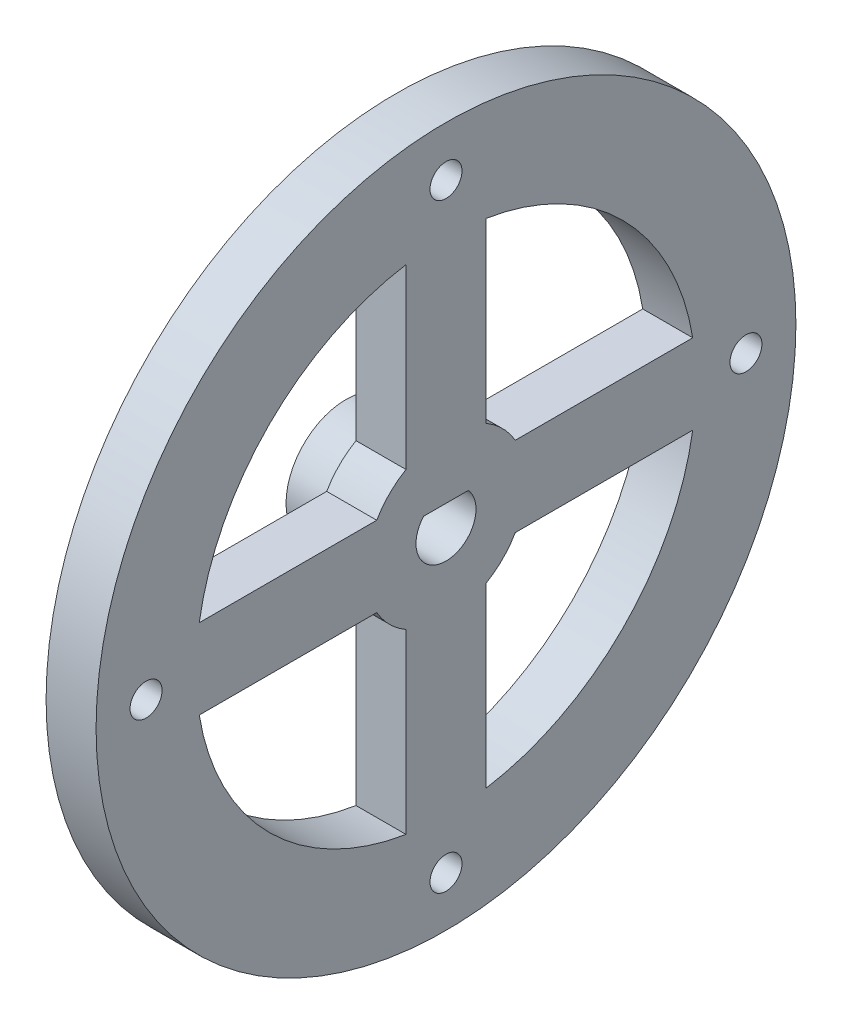
SolidWorks part; units mm, degrees
material "PLA (White)"
ref_plane "Front Plane" through (0, 0, 0) normal (0, 0, 1) x (1, 0, 0)
ref_plane "Top Plane" through (0, 0, 0) normal (0, 1, 0) x (1, 0, 0)
ref_plane "Right Plane" through (0, 0, 0) normal (1, 0, 0) x (0, 0, -1)
sketch "Sketch1" plane through (0, 0, 0) normal (1, 0, 0) x (0, 0, -1)
  line L0 (0, 0) -> (0, 50000) construction
  line L1 (4, 6.9282) -> (4, 24.6779)
  line L2 (-4, 24.6779) -> (-4, 6.9282)
  line L3 (-24.6779, -4) -> (-6.9282, -4)
  line L4 (-6.9282, 4) -> (-24.6779, 4)
  line L5 (4, -24.6779) -> (4, -6.9282)
  line L6 (-4, -6.9282) -> (-4, -24.6779)
  line L7 (24.6779, 4) -> (6.9282, 4)
  line L8 (6.9282, -4) -> (24.6779, -4)
  line L9 (-2.2361, 2) -> (2.2361, 2)
  circle A0 centre (0, 0) radius 35
  arc A1 (-2.2361, 2) -> (2.2361, 2) centre (0, 0) ccw
  arc A2 (-6.9282, -4) -> (-4, -6.9282) centre (0, 0) ccw
  arc A3 (-24.6779, -4) -> (-4, -24.6779) centre (0, 0) ccw
  arc A4 (-4, 6.9282) -> (-6.9282, 4) centre (0, 0) ccw
  arc A5 (24.6779, 4) -> (4, 24.6779) centre (0, 0) ccw
  arc A6 (4, -24.6779) -> (24.6779, -4) centre (0, 0) ccw
  arc A7 (4, -6.9282) -> (6.9282, -4) centre (0, 0) ccw
  arc A8 (6.9282, 4) -> (4, 6.9282) centre (0, 0) ccw
  arc A9 (-24.6779, 4) -> (-4, 24.6779) centre (0, 0) cw
  point P27 (0, 0)
  dimension "D1" = 70
  dimension "D2" = 6
  dimension "D5" = 16
  dimension "D6" = 50
  dimension "D3" = 8
  dimension "D7" = 2
  dimension "D4" = 4
extrude "Boss-Extrude1" add sketch "Sketch1" along normal blind 5
sketch "Sketch2" plane through (0, 0, 0) normal (-1, 0, 0) x (0, 0, 1)
  circle A0 centre (0, 0) radius 30 construction
  circle A1 centre (0, 30) radius 1.6
  circle A2 centre (30, 0) radius 1.6
  circle A3 centre (0, -30) radius 1.6
  circle A4 centre (-30, 0) radius 1.6
  point P14 (0, 0)
  dimension "D1" = 60
  dimension "D2" = 3.2
  dimension "D3" = 4
extrude "Cut-Extrude1" cut sketch "Sketch2" against normal through all
sketch "Sketch3" plane through (0, 0, 0) normal (-1, 0, 0) x (0, 0, 1)
  line L0 (-2.2361, 2) -> (2.2361, 2) construction
  line L1 (-2.2361, 2) -> (2.2361, 2)
  circle A2 centre (0, 0) radius 6
  arc A3 (-2.2361, 2) -> (2.2361, 2) centre (0, 0) ccw construction
  arc A4 (-2.2361, 2) -> (2.2361, 2) centre (0, 0) ccw
  dimension "D1" = 12
extrude "Boss-Extrude2" add sketch "Sketch3" along normal blind 5
sketch "Sketch6" plane through (0, 0, 0) normal (-1, 0, 0) x (0, 0, 1)
  circle A0 centre (0, 30) radius 4
  circle A1 centre (30, 0) radius 4
  circle A2 centre (0, -30) radius 4
  circle A3 centre (-30, 0) radius 4
  point P12 (0, 0)
  dimension "D1" = 8
  dimension "D2" = 4
extrude "Cut-Extrude2" cut sketch "Sketch6" against normal blind 2
